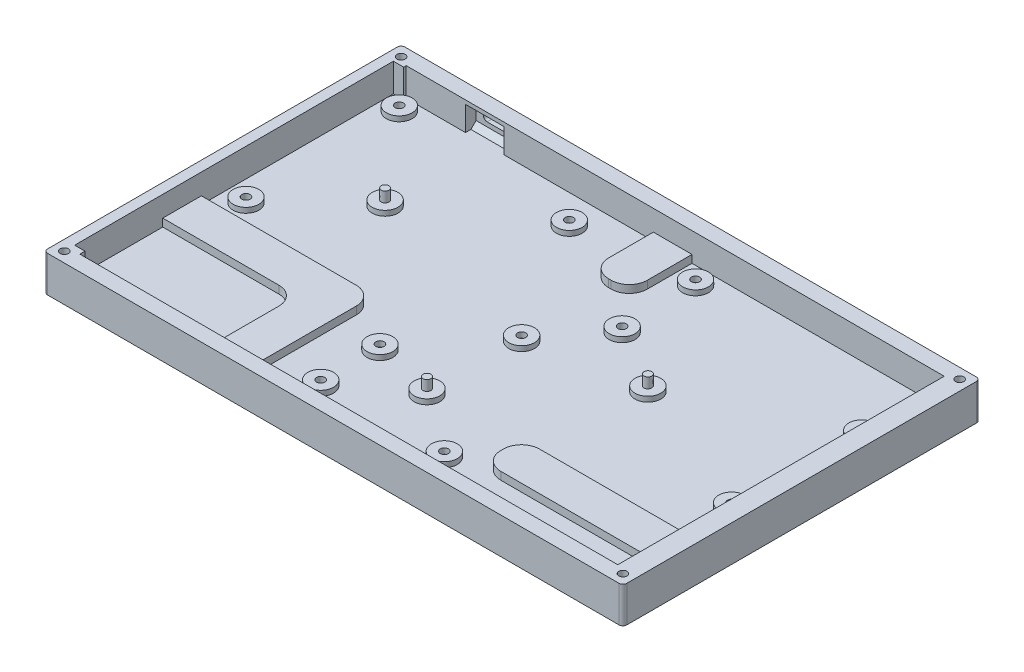
SolidWorks part; units mm, degrees
ref_plane "Front Plane" through (0, 0, 0) normal (0, 0, 1) x (1, 0, 0)
ref_plane "Top Plane" through (0, 0, 0) normal (0, 1, 0) x (1, 0, 0)
ref_plane "Right Plane" through (0, 0, 0) normal (1, 0, 0) x (0, 0, -1)
sketch "Sketch1" plane through (0, 0, 0) normal (0, 1, 0) x (1, 0, 0)
  line L1 (44.992, 213.0031) -> (269.802, 213.0031)
  line L2 (44.992, 213.0031) -> (44.992, 351.7031)
  line L3 (44.992, 351.7031) -> (269.802, 351.7031)
  line L4 (269.802, 213.0031) -> (269.802, 351.7031)
  dimension "D1" = 138.7
  dimension "D2" = 224.81
extrude "bottom_plate" add sketch "Sketch1" along normal blind 3
sketch "Sketch2" plane through (0, 3, 0) normal (0, 1, 0) x (1, 0, 0)
  line L9 (44.992, 213.0031) -> (52.992, 213.0031)
  line L10 (44.992, 213.0031) -> (44.992, 221.0031)
  line L11 (44.992, 221.0031) -> (52.992, 221.0031)
  line L12 (52.992, 213.0031) -> (52.992, 221.0031)
  line L13 (269.802, 213.0031) -> (262.802, 213.0031)
  line L14 (269.802, 213.0031) -> (269.802, 220.0031)
  line L15 (269.802, 220.0031) -> (262.802, 220.0031)
  line L16 (262.802, 213.0031) -> (262.802, 220.0031)
  line L17 (269.802, 351.7031) -> (262.802, 351.7031)
  line L18 (269.802, 351.7031) -> (269.802, 344.7031)
  line L19 (269.802, 344.7031) -> (262.802, 344.7031)
  line L20 (262.802, 351.7031) -> (262.802, 344.7031)
  line L21 (44.992, 351.7031) -> (52.992, 351.7031)
  line L22 (44.992, 351.7031) -> (44.992, 344.7031)
  line L23 (44.992, 344.7031) -> (52.992, 344.7031)
  line L24 (52.992, 351.7031) -> (52.992, 344.7031)
  dimension "D1" = 8
  dimension "D2" = 7
extrude "side_walls" add sketch "Sketch2" along normal blind 11
sketch "Sketch11" plane through (0, 3, 0) normal (0, 1, 0) x (1, 0, 0)
  line L0 (52.992, 221.0031) -> (44.992, 221.0031) construction
  line L1 (44.992, 344.7031) -> (48.992, 344.7031)
  line L2 (44.992, 344.7031) -> (44.992, 221.0031)
  line L3 (44.992, 221.0031) -> (48.992, 221.0031)
  line L4 (48.992, 344.7031) -> (48.992, 221.0031)
  line L5 (262.802, 220.0031) -> (262.802, 213.0031) construction
  line L6 (52.992, 213.0031) -> (262.802, 213.0031)
  line L7 (52.992, 213.0031) -> (52.992, 219.0031)
  line L8 (52.992, 219.0031) -> (261.802, 219.0031)
  line L9 (262.802, 213.0031) -> (262.802, 219.0031)
  line L11 (269.802, 219.0031) -> (262.802, 219.0031)
  line L12 (269.802, 219.0031) -> (269.802, 345.7031)
  line L13 (269.802, 345.7031) -> (262.802, 345.7031)
  line L14 (261.802, 219.0031) -> (261.802, 345.7031)
  line L15 (52.992, 344.7031) -> (52.992, 351.7031) construction
  line L16 (262.802, 351.7031) -> (52.992, 351.7031)
  line L17 (262.802, 351.7031) -> (262.802, 345.7031)
  line L18 (261.802, 345.7031) -> (90.992, 345.7031)
  line L19 (52.992, 351.7031) -> (52.992, 345.7031)
  line L20 (75.992, 345.7031) -> (52.992, 345.7031)
  line L22 (90.992, 345.7031) -> (90.992, 349.8031)
  line L23 (90.992, 349.8031) -> (75.992, 349.8031)
  line L24 (75.992, 345.7031) -> (75.992, 349.8031)
  line L25 (269.802, 220.0031) -> (269.802, 344.7031) construction
  dimension "D1" = 8
  dimension "D2" = 6
  dimension "D3" = 6
  dimension "D4" = 4
  dimension "D5" = 4.1
  dimension "D6" = 31
  dimension "D7" = 15
extrude "usb_cutout" add sketch "Sketch11" along normal up to surface (11 mm away) up to face at (266.302, 14, -216.5031)
hole_wizard "CSK for M3 SFHCS1" positions "Sketch5" profile "Sketch6" countersink size "M3" standard "ANSI Metric" end condition through all
sketch "Sketch5" plane through (0, 0, 0) normal (0, -1, 0) x (-1, 0, 0)
  point P42 (-48.992, 217.0037)
  point P45 (-265.7999, 217.0037)
  point P48 (-265.7999, 347.7031)
  point P51 (-48.992, 347.7031)
sketch "Sketch6" plane through (48.992, 0, -217.0037) normal (1, 0, 0) x (0, 0, -1)
  line L0 (0, 0) -> (0, 14)
  line L1 (0, 14) -> (1.6, 14)
  line L2 (1.6, 14) -> (1.6, 1.76)
  line L3 (1.6, 1.76) -> (3.36, 0)
  line L5 (3.36, 0) -> (0, 0)
  line L6 (-1.6, 1.76) -> (-3.36, 0) construction
  line L11 (0, -6.35) -> (0, 107.95) construction
  dimension "Thru Hole Dia." = 3.2
  dimension "Thru Hole Depth" = 14
  dimension "Near C'Sink Dia." = 6.72
  dimension "Near C'Sink Angle" = 90
fillet "Fillet1" radius 1.5 4 edges at (44.992, 7, -351.7031) (44.992, 7, -213.0031) (269.802, 7, -351.7031) (269.802, 7, -213.0031)
sketch "Sketch14" plane through (0, 0, -349.8031) normal (0, 0, 1) x (1, 0, 0)
  line L0 (44.992, 14) -> (44.992, 0) construction
  line L9 (80.3002, 6.7) -> (86.4707, 6.7)
  line L10 (78.8002, 8.2) -> (78.8002, 8.5905)
  line L11 (80.3002, 10.0905) -> (86.4707, 10.0905)
  line L12 (87.9707, 8.2) -> (87.9707, 8.5905)
  line L13 (268.302, 0) -> (46.492, 0) construction
  arc A4 (78.8002, 8.5905) -> (80.3002, 10.0905) centre (80.3002, 8.5905) cw
  arc A5 (80.3002, 6.7) -> (78.8002, 8.2) centre (80.3002, 8.2) cw
  arc A6 (86.4707, 6.7) -> (87.9707, 8.2) centre (86.4707, 8.2) ccw
  arc A7 (86.4707, 10.0905) -> (87.9707, 8.5905) centre (86.4707, 8.5905) cw
  dimension "D1" = 9.1705
  dimension "D5" = 1.5
  dimension "D2" = 3.3905
  dimension "D3" = 33.8083
  dimension "D4" = 6.7
extrude "usb-c port" cut sketch "Sketch14" against normal blind 10
sketch "Sketch18" plane through (0, 14, 0) normal (0, 1, 0) x (1, 0, 0)
  line L1 (75.992, 345.7031) -> (90.992, 345.7031)
  line L2 (75.992, 345.7031) -> (75.992, 349.8031)
  line L3 (75.992, 349.8031) -> (90.992, 349.8031)
  line L4 (90.992, 345.7031) -> (90.992, 349.8031)
extrude "Boss-Extrude1" add sketch "Sketch18" against normal blind 1.5
chamfer "Chamfer1" distance 2 angle 45 2 edges at (83.492, 3, -349.8031) (83.492, 12.5, -349.8031)
sketch "Sketch16" plane through (0, 3, 0) normal (0, 1, 0) x (1, 0, 0)
  circle A0 centre (55.992, 340.0037) radius 5
  circle A1 centre (56.992, 279.5037) radius 5
  circle A2 centre (132.492, 256.0037) radius 5
  circle A4 centre (253.992, 271.0037) radius 5
  circle A5 centre (254.992, 320.5037) radius 5
  circle A6 centre (156.992, 286.5037) radius 5
  circle A7 centre (171.992, 339.0037) radius 5
  circle A8 centre (127.492, 334.5037) radius 5
  circle A9 centre (173.492, 309.0037) radius 5
  circle A10 centre (198.492, 294.0037) radius 5
  circle A11 centre (180.992, 232.5037) radius 5
  circle A12 centre (84.992, 305.5037) radius 5
  circle A15 centre (156.492, 250.2537) radius 5
  circle A29 centre (132.992, 232.5037) radius 5
  dimension "D1" = 10
extrude "pcb_support" add sketch "Sketch16" along normal blind 2 contours A0 | A12 | A1 | A7 | A8 | A6 | A11 | A10 | A5 | A4 | A9 | A2 | A15 | A29 region at (55.992, 3, -340.0037) region at (56.992, 3, -279.5037) region at (253.992, 3, -271.0037) region at (254.992, 3, -320.5037) region at (156.992, 3, -286.5037) region at (171.992, 3, -339.0037) region at (127.492, 3, -334.5037) region at (198.492, 3, -294.0037) region at (180.992, 3, -232.5037) region at (84.992, 3, -305.5037)
sketch "Sketch17" plane through (0, 5, 0) normal (0, 1, 0) x (1, 0, 0)
  circle A0 centre (84.992, 305.5037) radius 1.5
  circle A1 centre (198.492, 294.0037) radius 1.5
  circle A2 centre (84.992, 305.5037) radius 5 construction
  circle A3 centre (156.492, 250.2537) radius 1.5
  dimension "D1" = 3
  dimension "D2" = 3
  dimension "D3" = 3
extrude "alignment_posts" add sketch "Sketch17" along normal blind 4
sketch "Sketch20" plane through (0, 5, 0) normal (0, 1, 0) x (1, 0, 0)
  circle A0 centre (55.992, 340.0037) radius 1.6
  circle A1 centre (127.492, 334.5037) radius 1.6
  circle A2 centre (56.992, 279.5037) radius 1.6
  circle A3 centre (132.492, 256.0037) radius 1.6
  circle A4 centre (132.992, 232.5037) radius 1.6
  circle A5 centre (180.992, 232.5037) radius 1.6
  circle A6 centre (156.992, 286.5037) radius 1.6
  circle A7 centre (253.992, 271.0037) radius 1.6
  circle A8 centre (173.492, 309.0037) radius 1.6
  circle A9 centre (171.992, 339.0037) radius 1.6
  circle A10 centre (254.992, 320.5037) radius 1.6
  dimension "D1" = 3.2
extrude "pcb screw clearance" cut sketch "Sketch20" against normal blind 2.15
sketch "Sketch21" plane through (0, 2.85, 0) normal (0, 1, 0) x (1, 0, 0)
  line L0 (154.242, 283.7537) -> (159.742, 283.7537)
  line L1 (53.242, 342.7537) -> (58.742, 342.7537)
  line L2 (53.242, 342.7537) -> (53.242, 337.2537)
  line L3 (53.242, 337.2537) -> (58.742, 337.2537)
  line L4 (58.742, 342.7537) -> (58.742, 337.2537)
  line L5 (53.242, 342.7537) -> (58.742, 337.2537) construction
  line L6 (53.242, 337.2537) -> (58.742, 342.7537) construction
  line L7 (124.742, 337.2537) -> (130.242, 337.2537)
  line L8 (124.742, 337.2537) -> (124.742, 331.7537)
  line L9 (124.742, 331.7537) -> (130.242, 331.7537)
  line L10 (130.242, 337.2537) -> (130.242, 331.7537)
  line L11 (124.742, 337.2537) -> (130.242, 331.7537) construction
  line L12 (124.742, 331.7537) -> (130.242, 337.2537) construction
  line L13 (54.242, 282.2537) -> (59.742, 282.2537)
  line L14 (54.242, 282.2537) -> (54.242, 276.7537)
  line L15 (54.242, 276.7537) -> (59.742, 276.7537)
  line L16 (59.742, 282.2537) -> (59.742, 276.7537)
  line L17 (54.242, 282.2537) -> (59.742, 276.7537) construction
  line L18 (54.242, 276.7537) -> (59.742, 282.2537) construction
  line L19 (129.742, 258.7537) -> (135.242, 258.7537)
  line L20 (129.742, 258.7537) -> (129.742, 253.2537)
  line L21 (129.742, 253.2537) -> (135.242, 253.2537)
  line L22 (135.242, 258.7537) -> (135.242, 253.2537)
  line L23 (129.742, 258.7537) -> (135.242, 253.2537) construction
  line L24 (129.742, 253.2537) -> (135.242, 258.7537) construction
  line L25 (135.742, 235.2537) -> (130.242, 235.2537)
  line L26 (135.742, 235.2537) -> (135.742, 229.7537)
  line L27 (135.742, 229.7537) -> (130.242, 229.7537)
  line L28 (130.242, 235.2537) -> (130.242, 229.7537)
  line L29 (135.742, 235.2537) -> (130.242, 229.7537) construction
  line L30 (135.742, 229.7537) -> (130.242, 235.2537) construction
  line L31 (178.242, 229.7537) -> (183.742, 229.7537)
  line L32 (178.242, 229.7537) -> (178.242, 235.2537)
  line L33 (178.242, 235.2537) -> (183.742, 235.2537)
  line L34 (183.742, 229.7537) -> (183.742, 235.2537)
  line L35 (178.242, 229.7537) -> (183.742, 235.2537) construction
  line L36 (178.242, 235.2537) -> (183.742, 229.7537) construction
  line L37 (256.742, 273.7537) -> (251.242, 273.7537)
  line L38 (256.742, 273.7537) -> (256.742, 268.2537)
  line L39 (256.742, 268.2537) -> (251.242, 268.2537)
  line L40 (251.242, 273.7537) -> (251.242, 268.2537)
  line L41 (256.742, 273.7537) -> (251.242, 268.2537) construction
  line L42 (256.742, 268.2537) -> (251.242, 273.7537) construction
  line L43 (170.742, 306.2537) -> (176.242, 306.2537)
  line L44 (170.742, 306.2537) -> (170.742, 311.7537)
  line L45 (170.742, 311.7537) -> (176.242, 311.7537)
  line L46 (176.242, 306.2537) -> (176.242, 311.7537)
  line L47 (170.742, 306.2537) -> (176.242, 311.7537) construction
  line L48 (170.742, 311.7537) -> (176.242, 306.2537) construction
  line L49 (169.242, 336.2537) -> (174.742, 336.2537)
  line L50 (169.242, 336.2537) -> (169.242, 341.7537)
  line L51 (169.242, 341.7537) -> (174.742, 341.7537)
  line L52 (174.742, 336.2537) -> (174.742, 341.7537)
  line L53 (169.242, 336.2537) -> (174.742, 341.7537) construction
  line L54 (169.242, 341.7537) -> (174.742, 336.2537) construction
  line L55 (252.242, 317.7537) -> (257.742, 317.7537)
  line L56 (252.242, 317.7537) -> (252.242, 323.2537)
  line L57 (252.242, 323.2537) -> (257.742, 323.2537)
  line L58 (257.742, 317.7537) -> (257.742, 323.2537)
  line L59 (252.242, 317.7537) -> (257.742, 323.2537) construction
  line L60 (252.242, 323.2537) -> (257.742, 317.7537) construction
  line L61 (154.242, 283.7537) -> (154.242, 289.2537)
  line L62 (154.242, 289.2537) -> (159.742, 289.2537)
  line L63 (159.742, 283.7537) -> (159.742, 289.2537)
  line L64 (154.242, 283.7537) -> (159.742, 289.2537) construction
  line L65 (154.242, 289.2537) -> (159.742, 283.7537) construction
  point P0 (55.992, 340.0037)
  point P6 (127.492, 334.5037)
  point P12 (56.992, 279.5037)
  point P18 (132.492, 256.0037)
  point P24 (132.992, 232.5037)
  point P30 (180.992, 232.5037)
  point P36 (253.992, 271.0037)
  point P42 (173.492, 309.0037)
  point P48 (171.992, 339.0037)
  point P54 (254.992, 320.5037)
  point P60 (156.992, 286.5037)
  dimension "D1" = 5.5
extrude "captive nut hole" cut sketch "Sketch21" against normal blind 1.8
sketch "Sketch22" plane through (0, 3, 0) normal (0, 1, 0) x (1, 0, 0)
  line L0 (48.992, 221.0031) -> (48.992, 344.7031) construction
  line L1 (48.992, 270.1949) -> (109.1049, 270.1949)
  line L2 (48.992, 270.1949) -> (48.992, 255.1949)
  line L3 (48.992, 255.1949) -> (94.1049, 255.1949)
  line L4 (116.1049, 263.1949) -> (116.1049, 255.1949)
  line L5 (261.802, 345.7031) -> (261.802, 219.0031) construction
  line L6 (261.802, 250.6959) -> (199.7247, 250.6959)
  line L7 (261.802, 250.6959) -> (261.802, 235.6959)
  line L8 (261.802, 235.6959) -> (199.7247, 235.6959)
  line L9 (192.7247, 243.6959) -> (192.7247, 242.6959)
  line L10 (52.992, 345.7031) -> (261.802, 345.7031) construction
  line L11 (148.9092, 345.7031) -> (163.9092, 345.7031)
  line L12 (148.9092, 345.7031) -> (148.9092, 328.3512)
  line L13 (155.9092, 321.3512) -> (156.9092, 321.3512)
  line L14 (163.9092, 345.7031) -> (163.9092, 328.3512)
  line L15 (261.802, 219.0031) -> (52.992, 219.0031) construction
  line L16 (116.1049, 219.0031) -> (101.1049, 219.0031)
  line L17 (116.1049, 219.0031) -> (116.1049, 255.1949)
  line L19 (101.1049, 219.0031) -> (101.1049, 248.1949)
  arc A0 (94.1049, 255.1949) -> (101.1049, 248.1949) centre (94.1049, 248.1949) cw
  arc A1 (156.9092, 321.3512) -> (163.9092, 328.3512) centre (156.9092, 328.3512) ccw
  arc A2 (148.9092, 328.3512) -> (155.9092, 321.3512) centre (155.9092, 328.3512) ccw
  arc A3 (199.7247, 235.6959) -> (192.7247, 242.6959) centre (199.7247, 242.6959) cw
  arc A4 (199.7247, 250.6959) -> (192.7247, 243.6959) centre (199.7247, 243.6959) ccw
  arc A5 (109.1049, 270.1949) -> (116.1049, 263.1949) centre (109.1049, 263.1949) cw
  point P20 (116.1049, 270.1949)
  point P24 (48.992, 270.1949)
  point P25 (94.7707, 248.4018)
  point P26 (110.5993, 253.6781)
  point P27 (192.7247, 250.6959)
  point P28 (148.9092, 321.3512)
  dimension "D2" = 7
  dimension "D1" = 15
extrude "Boss-Extrude2" add sketch "Sketch22" along normal blind 3
